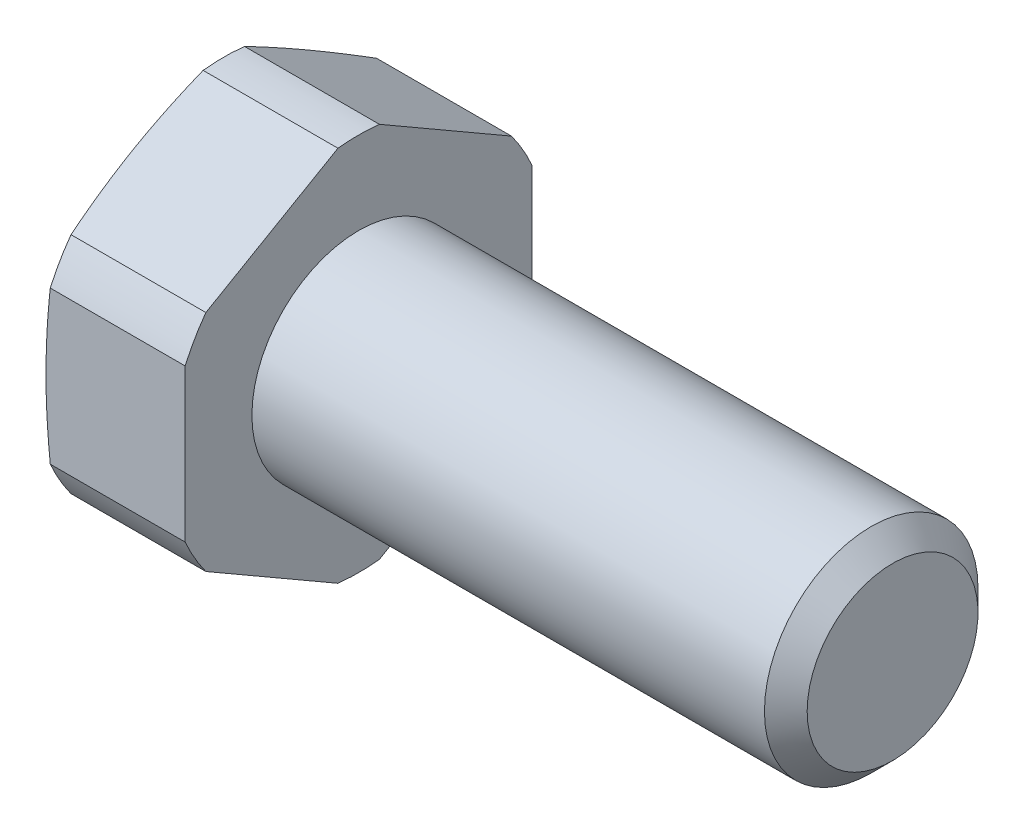
SolidWorks part; units mm, degrees
material "AISI 1020"
ref_plane "Спереди" through (0, 0, 0) normal (0, 0, 1) x (1, 0, 0)
ref_plane "Сверху" through (0, 0, 0) normal (0, 1, 0) x (1, 0, 0)
ref_plane "Справа" through (0, 0, 0) normal (1, 0, 0) x (0, 0, -1)
sketch "Эскиз1" plane through (0, 0, 0) normal (0, 0, 1) x (1, 0, 0)
  line L0 (-1000, 0) -> (49000, 0) construction
  line L1 (-5.3, 0) -> (-5.3, 6.175)
  line L2 (-5.3, 6.175) -> (-5.0521, 7.1)
  line L3 (-5.0521, 7.1) -> (0, 7.1)
  line L4 (0, 7.1) -> (0, 4)
  line L5 (0, 4) -> (19.2, 4)
  line L6 (20, 3.2) -> (20, 0)
  line L7 (20, 4) -> (20.625, 5.0825) construction
  line L8 (20.625, 5.0825) -> (21.25, 4) construction
  line L9 (21.25, 4) -> (20, 4) construction
  line L10 (20.625, 5.0825) -> (20.625, 4) construction
  line L11 (20.625, 5.0825) -> (0.625, 5.0825) construction
  line L12 (19.2, 4) -> (20, 3.2)
  line L13 (20, 4) -> (19.6, 3.6) construction
  line L14 (-5.3, 6.175) -> (-18.3, 6.175) construction
  line L15 (-5.3, 0) -> (20, 0)
  dimension "D1" = 0.8
  dimension "D2" = 15
revolve "Повернуть1" add sketch "Эскиз1" angle 360 about L0
cosmetic thread "Условное изображение резьбы1" parameters "D1"=20, "D2"=5.8349
sketch "Эскиз2" plane through (-5.3, 0, 0) normal (-1, 0, 0) x (0, 0, 1)
  line L1 (0, 7.5056) -> (-6.5, 3.7528)
  line L2 (-6.5, 3.7528) -> (-6.5, -3.7528)
  line L3 (-6.5, -3.7528) -> (0, -7.5056)
  line L4 (0, -7.5056) -> (6.5, -3.7528)
  line L5 (6.5, -3.7528) -> (6.5, 3.7528)
  line L6 (6.5, 3.7528) -> (0, 7.5056)
  circle A0 centre (0, 0) radius 6.5 construction
  dimension "D1" = 13
extrude "Вырез-Вытянуть1" cut sketch "Эскиз2" against normal up to surface (25.3 mm away) flip side to cut up to face at (20, 0, 3.2)
equation "\"D1@Эскиз1\"=\"_d_@Эскиз1\"/10"
equation "\"D@Эскиз1\"=\"S_@Эскиз1\"*0.95"
equation "\"D1@Эскиз2\"=\"S_@Эскиз1\""
equation "\"D1@Условное изображение резьбы1\"=\"b_@Эскиз1\""
equation "\"D2@Условное изображение резьбы1\"=\"_d_@Эскиз1\"-\"dr@Эскиз1\"*2"
